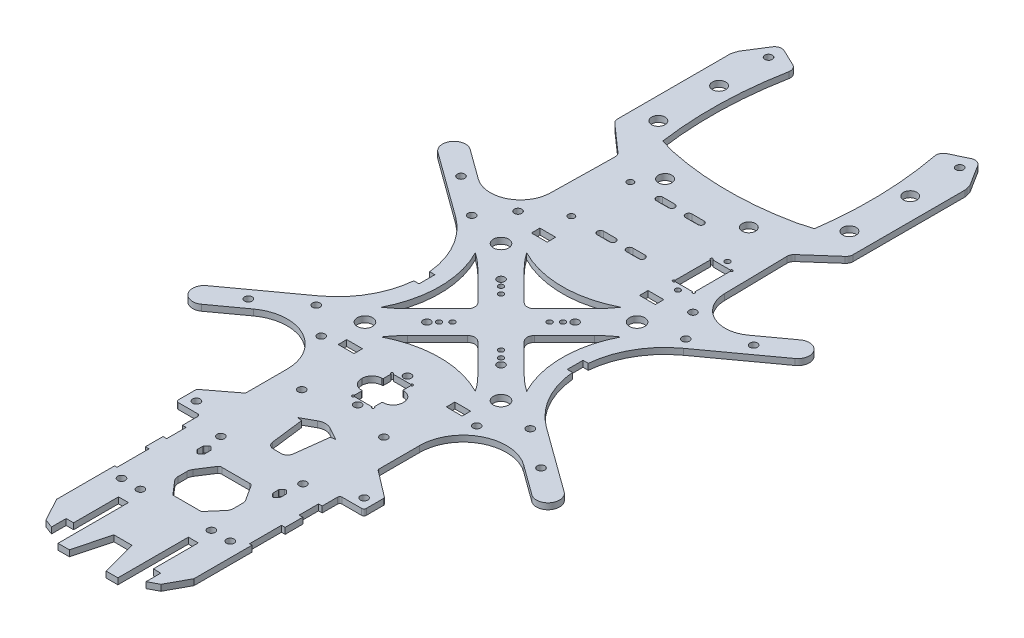
SolidWorks part; units mm, degrees
material "PPS"
ref_plane "前视基准面" through (0, 0, 0) normal (0, 0, 1) x (1, 0, 0)
ref_plane "上视基准面" through (0, 0, 0) normal (0, 1, 0) x (1, 0, 0)
ref_plane "右视基准面" through (0, 0, 0) normal (1, 0, 0) x (0, 0, -1)
sketch "草图1" plane through (0, 0, 0) normal (0, 1, 0) x (1, 0, 0)
  line L0 (-126.4995, 0) -> (116.8967, 0) construction
  line L1 (121.619, 121.619) -> (-121.619, -121.619) construction
  line L2 (0, 104.5414) -> (0, -99.6328) construction
  line L3 (-108.3893, 108.3893) -> (124.9236, -124.9236) construction
  line L4 (0, 0) -> (86.3378, -62.728) construction
  line L5 (21.4, 65.75) -> (28.6, 65.75)
  line L6 (20.9, 50.75) -> (20.9, 65.25)
  line L19 (21.4, 50.25) -> (28.6, 50.25)
  line L20 (35.3841, 83.6272) -> (48.4165, 95.1336)
  line L21 (0, 82.79) -> (0, 88.225) construction
  line L22 (17.0991, -107.7737) -> (17.0991, -105.6162)
  line L23 (-25.2781, 96.1111) -> (-31.2329, 97.7907)
  line L25 (27.2573, -95.1) -> (28.7573, -95.1) construction
  line L28 (15.9026, -104.2126) -> (16.9526, -105.2626)
  line L29 (14.1455, -105.2626) -> (15.1955, -104.2126)
  line L30 (-16.9545, -108.1273) -> (-15.9045, -109.1773)
  line L35 (73.5338, -47.5541) -> (46.853, -28.1694)
  line L36 (-15.1974, -109.1773) -> (-14.1474, -108.1273)
  line L37 (-14.0009, -105.6162) -> (-14.0009, -107.7737)
  line L38 (-14.1474, -105.2626) -> (-15.1974, -104.2126)
  line L39 (-48.4165, 95.1336) -> (-48.4165, 143.0516)
  line L40 (-35.3841, 83.6272) -> (-48.4165, 95.1336)
  line L42 (28.7573, -95.1) -> (28.7573, -102.35)
  line L59 (0, 72.0242) -> (0, 60.8242) construction
  line L64 (20.9, 58) -> (32.4846, 58) construction
  line L65 (25, 65.75) -> (25, 50.25) construction
  line L66 (29.1, 65.25) -> (29.1, 50.75)
  line L69 (-28.3, 64.3716) -> (-2.5276, 64.3716) construction
  line L72 (28.7573, -102.35) -> (27.2573, -102.35)
  line L80 (-15.9045, -104.2126) -> (-16.9545, -105.2626)
  line L81 (-17.1009, -107.7737) -> (-17.1009, -105.6162)
  line L82 (4.1009, -56.25) -> (4.1009, -53.2975)
  line L83 (-3.6009, -56.75) -> (3.6009, -56.75)
  line L84 (3.6009, -40.75) -> (-3.5991, -40.75)
  line L85 (4.1009, -41.25) -> (4.1009, -44.2025)
  line L86 (-4.1009, -56.25) -> (-4.1009, -53.2961)
  line L87 (-4.1009, -44.2011) -> (-4.1009, -41.2481)
  line L88 (-4.5484, -52.9461) -> (-4.4509, -52.9461)
  line L89 (-8.5484, -48.9461) -> (-8.5484, -48.5511)
  line L90 (8.5484, -48.9475) -> (8.5484, -48.5525)
  line L91 (4.4509, -52.9475) -> (4.5484, -52.9475)
  line L92 (4.5484, -44.5525) -> (4.4509, -44.5525)
  line L93 (-4.5484, -44.5511) -> (-4.4509, -44.5511)
  line L94 (13.9991, -105.6162) -> (13.9991, -107.7737)
  line L95 (15.1955, -109.1773) -> (14.1455, -108.1273)
  line L96 (16.9526, -108.1273) -> (15.9026, -109.1773)
  line L97 (18.9991, -62.5) -> (18.9991, -100.5) construction
  line L98 (18.9991, -100.5) -> (-19.0009, -100.5) construction
  line L99 (-19.0009, -62.5) -> (-19.0009, -100.5) construction
  line L100 (27.2573, -102.35) -> (27.2573, -110.35)
  line L101 (16.4174, -141.0041) -> (16.4174, -159.5041)
  line L102 (16.4174, -141.0041) -> (12.3174, -141.0041)
  line L103 (12.3174, -141.0041) -> (12.3174, -170.0041)
  line L104 (19.4666, -159.5041) -> (16.4174, -159.5041)
  line L105 (19.4666, -165.5542) -> (19.4666, -159.5041)
  line L106 (-3.8169, -155.5041) -> (-7.6919, -170.0041)
  line L107 (-7.6919, -170.0041) -> (-12.3174, -170.0041)
  line L108 (23.4926, -163.4505) -> (19.4666, -165.5542)
  line L109 (-19.4666, -165.5542) -> (-19.4666, -159.5041)
  line L110 (-19.4666, -159.5041) -> (-16.4174, -159.5041)
  line L111 (-12.3174, -141.0041) -> (-12.3174, -170.0041)
  line L112 (-16.4174, -141.0041) -> (-12.3174, -141.0041)
  line L113 (-16.4174, -141.0041) -> (-16.4174, -159.5041)
  line L114 (7.4592, -170.0041) -> (12.3174, -170.0041)
  line L115 (-3.8169, -155.5041) -> (3.6009, -155.5041)
  line L116 (3.6009, -155.5041) -> (7.4592, -170.0041)
  line L117 (-23.1028, -164.168) -> (-19.4666, -165.5542)
  line L118 (-10.8641, -115.9341) -> (-6.9283, -109.8213)
  line L119 (-10.5808, -123.7337) -> (-5.8541, -129.2069)
  line L120 (-5.8541, -129.2069) -> (5.8541, -129.2069)
  line L121 (-11.4015, -121.5278) -> (-11.4015, -117.7612)
  line L122 (27.2573, -110.35) -> (28.7573, -110.35)
  line L123 (28.2798, -130.7335) -> (28.2798, -154.6401)
  line L124 (28.2798, -154.6401) -> (23.4926, -163.4505)
  line L125 (-28.2798, -154.6401) -> (-23.1028, -164.168)
  line L126 (-28.2798, -130.7335) -> (-28.2798, -154.6401)
  line L127 (28.7573, -110.35) -> (28.7573, -117.6)
  line L128 (28.7573, -117.6) -> (27.2573, -117.6)
  line L129 (27.2573, -117.6) -> (27.2573, -130.7962)
  line L130 (27.2573, -130.7962) -> (28.2798, -130.7335)
  line L132 (-27.2573, -130.7962) -> (-28.2798, -130.7335)
  line L133 (-27.2573, -117.6) -> (-27.2573, -130.7962)
  line L134 (-28.7573, -117.6) -> (-27.2573, -117.6)
  line L135 (-28.7573, -110.35) -> (-28.7573, -117.6)
  line L136 (-27.2573, -110.35) -> (-28.7573, -110.35)
  line L137 (-27.2573, -102.35) -> (-27.2573, -110.35)
  line L138 (-28.7573, -102.35) -> (-27.2573, -102.35)
  line L139 (-28.7573, -95.1) -> (-28.7573, -102.35)
  line L140 (-27.2573, -95.1) -> (-28.7573, -95.1) construction
  line L142 (-73.5338, 47.5541) -> (-46.853, 28.1694)
  line L143 (-73.5338, -47.5541) -> (-46.853, -28.1694)
  line L149 (48.4165, 95.1336) -> (48.4165, 143.0516)
  line L150 (0, -114.8485) -> (0, -146.3095) construction
  line L151 (-5.6802, -109.2069) -> (5.6802, -109.2069)
  line L152 (10.5808, -123.7337) -> (5.8541, -129.2069)
  line L153 (11.4015, -121.5278) -> (11.4015, -117.7612)
  line L154 (10.8641, -115.9341) -> (6.9283, -109.8213)
  line L155 (-19.0009, -62.5) -> (18.9991, -62.5) construction
  line L166 (-11.2799, 76.5216) -> (-6.2799, 76.5216) construction
  line L169 (-11.2799, 77.8216) -> (-6.2799, 77.8216)
  line L170 (-11.2799, 75.2216) -> (-6.2799, 75.2216)
  line L171 (-11.2799, 52.2216) -> (-6.2799, 52.2216) construction
  line L172 (-11.2799, 50.9216) -> (-6.2799, 50.9216)
  line L173 (-11.2799, 53.5216) -> (-6.2799, 53.5216)
  line L174 (5.7201, 76.5216) -> (0.7201, 76.5216) construction
  line L175 (5.7201, 75.2216) -> (0.7201, 75.2216)
  line L176 (5.7201, 77.8216) -> (0.7201, 77.8216)
  line L177 (5.7201, 52.2216) -> (0.7201, 52.2216) construction
  line L178 (5.7201, 53.5216) -> (0.7201, 53.5216)
  line L179 (5.7201, 50.9216) -> (0.7201, 50.9216)
  line L180 (73.5338, 47.5541) -> (46.853, 28.1694)
  line L181 (44.0442, 32) -> (60.2246, 43.7557) construction
  line L183 (25.2781, 96.1111) -> (31.2329, 97.7907)
  line L184 (47.6512, 145.4189) -> (48.4165, 143.0516)
  line L188 (-47.6512, 145.4189) -> (-40.8875, 156.1591)
  line L190 (47.6512, 145.4189) -> (40.8875, 156.1591)
  line L192 (31.6811, 151.7709) -> (40.8875, 156.1591)
  line L193 (-40.8875, 156.1591) -> (-31.6811, 151.7709)
  line L194 (-47.6512, 145.4189) -> (-48.4165, 143.0516)
  line L195 (67.9498, 55.2397) -> (55.6247, 46.285)
  line L196 (35.3841, 83.6272) -> (35.8675, 56.1341)
  line L197 (-35.3841, 83.6272) -> (-35.8675, 56.1341)
  line L198 (-67.9498, 55.2397) -> (-55.6247, 46.285)
  line L199 (55.6018, -46.2684) -> (67.9498, -55.2397)
  line L200 (27.2573, -60.7106) -> (27.2573, -95.1) construction
  line L201 (-27.2573, -60.7106) -> (-27.2573, -95.1) construction
  line L202 (-55.6018, -46.2684) -> (-67.9498, -55.2397)
  line L203 (28.7573, -95.1) -> (38.6804, -95.1)
  line L204 (38.6804, -95.1) -> (38.6804, -86.6)
  line L205 (38.6804, -86.6) -> (27.2573, -77.9053)
  line L206 (27.2573, -60.7106) -> (27.2573, -77.9053)
  line L207 (-38.6804, -86.6) -> (-27.2573, -77.9053)
  line L208 (-38.6804, -95.1) -> (-38.6804, -86.6)
  line L209 (-28.7573, -95.1) -> (-38.6804, -95.1)
  line L210 (-27.2573, -60.7106) -> (-27.2573, -77.9053)
  circle A0 centre (10, 10) radius 1.075
  circle A1 centre (12.75, 12.75) radius 1.075
  circle A2 centre (15.25, 15.25) radius 1.55
  circle A3 centre (-15.25, 15.25) radius 1.55
  circle A4 centre (-12.75, 12.75) radius 1.075
  circle A5 centre (-10, 10) radius 1.075
  circle A6 centre (-10, -10) radius 1.075
  circle A7 centre (-12.75, -12.75) radius 1.075
  circle A8 centre (-15.25, -15.25) radius 1.55
  circle A9 centre (15.25, -15.25) radius 1.55
  circle A10 centre (12.75, -12.75) radius 1.075
  circle A11 centre (10, -10) radius 1.075
  circle A14 centre (28, -28) radius 3.15
  circle A15 centre (-28, -28) radius 3.15
  circle A16 centre (25, 68.2) radius 1.05
  arc A17 (20.9, 65.25) -> (21.4, 65.75) centre (20.9, 65.75) cw
  arc A18 (20.9, 50.75) -> (21.4, 50.25) centre (20.9, 50.25) ccw
  circle A31 centre (25, 47.8) radius 1.05
  circle A34 centre (17.238, 84.7633) radius 2.75
  circle A35 centre (-17.238, 84.7633) radius 2.75
  circle A36 centre (-39.335, 104.0823) radius 2.75
  circle A37 centre (-39.335, 129.0823) radius 2.75
  circle A38 centre (-28, 28) radius 3.15
  circle A39 centre (28, 28) radius 3.15
  circle A43 centre (44.0442, -32) radius 1.55
  circle A44 centre (60.2246, -43.7557) radius 1.55
  circle A47 centre (-60.2246, -43.7557) radius 1.55
  arc A63 (29.1, 65.25) -> (28.6, 65.75) centre (29.1, 65.75) ccw
  arc A64 (29.1, 50.75) -> (28.6, 50.25) centre (29.1, 50.25) cw
  circle A65 centre (-23.2799, 76.5216) radius 1.3
  circle A68 centre (-23.2799, 52.2216) radius 1.3
  circle A71 centre (-44.0442, -32) radius 1.55
  circle A72 centre (60.2246, 43.7557) radius 1.55
  circle A73 centre (44.0442, 32) radius 1.55
  circle A74 centre (-44.0442, 32) radius 1.55
  circle A75 centre (-60.2246, 43.7557) radius 1.55
  arc A76 (-11.2799, 77.8216) -> (-11.2799, 75.2216) centre (-11.2799, 76.5216) ccw
  arc A77 (67.9498, -55.2397) -> (73.5338, -47.5541) centre (70.7418, -51.3969) ccw
  arc A79 (-17.1009, -107.7737) -> (-16.9545, -108.1273) centre (-16.6009, -107.7737) ccw
  arc A80 (-15.9045, -109.1773) -> (-15.1974, -109.1773) centre (-15.5509, -108.8237) ccw
  arc A81 (-14.0009, -107.7737) -> (-14.1474, -108.1273) centre (-14.5009, -107.7737) cw
  arc A82 (-14.0009, -105.6162) -> (-14.1474, -105.2626) centre (-14.5009, -105.6162) ccw
  arc A83 (-15.1974, -104.2126) -> (-15.9045, -104.2126) centre (-15.5509, -104.5662) ccw
  arc A84 (-17.1009, -105.6162) -> (-16.9545, -105.2626) centre (-16.6009, -105.6162) cw
  arc A85 (-4.1009, -56.25) -> (-3.6009, -56.75) centre (-4.1009, -56.75) ccw
  arc A86 (4.1009, -56.25) -> (3.6009, -56.75) centre (4.1009, -56.75) cw
  arc A87 (4.1009, -41.25) -> (3.6009, -40.75) centre (4.1009, -40.75) ccw
  arc A88 (-4.1009, -41.2481) -> (-3.5991, -40.75) centre (-4.0991, -40.7481) cw
  arc A89 (8.5484, -48.5525) -> (4.5484, -44.5525) centre (4.5484, -48.5525) ccw
  arc A90 (-4.5484, -44.5511) -> (-8.5484, -48.5511) centre (-4.5484, -48.5511) ccw
  arc A91 (-4.5484, -52.9461) -> (-8.5484, -48.9461) centre (-4.5484, -48.9461) cw
  arc A92 (8.5484, -48.9475) -> (4.5484, -52.9475) centre (4.5484, -48.9475) cw
  arc A93 (4.1009, -44.2025) -> (4.4509, -44.5525) centre (4.4509, -44.2025) ccw
  arc A94 (4.1009, -53.2975) -> (4.4509, -52.9475) centre (4.4509, -53.2975) cw
  arc A95 (-4.1009, -44.2011) -> (-4.4509, -44.5511) centre (-4.4509, -44.2011) cw
  arc A96 (-4.1009, -53.2961) -> (-4.4509, -52.9461) centre (-4.4509, -53.2961) ccw
  arc A97 (17.0991, -107.7737) -> (16.9526, -108.1273) centre (16.5991, -107.7737) cw
  arc A98 (17.0991, -105.6162) -> (16.9526, -105.2626) centre (16.5991, -105.6162) ccw
  arc A99 (15.1955, -104.2126) -> (15.9026, -104.2126) centre (15.5491, -104.5662) cw
  arc A100 (13.9991, -105.6162) -> (14.1455, -105.2626) centre (14.4991, -105.6162) cw
  arc A101 (13.9991, -107.7737) -> (14.1455, -108.1273) centre (14.4991, -107.7737) ccw
  arc A102 (15.9026, -109.1773) -> (15.1955, -109.1773) centre (15.5491, -108.8237) cw
  circle A103 centre (-22.3899, -133.8062) radius 1.55
  circle A104 centre (22.3899, -133.8062) radius 1.55
  circle A105 centre (-16.9009, -98.4) radius 1.55
  circle A106 centre (16.8991, -98.4) radius 1.55
  arc A107 (-5.6802, -109.2069) -> (-6.9283, -109.8213) centre (-5.7932, -110.5521) ccw
  arc A108 (-11.4015, -117.7612) -> (-10.8641, -115.9341) centre (-8.0265, -117.7612) cw
  arc A109 (-10.5808, -123.7337) -> (-11.4015, -121.5278) centre (-8.0265, -121.5278) cw
  circle A110 centre (-14.6009, -133.8062) radius 1.55
  circle A111 centre (14.6009, -133.8062) radius 1.55
  arc A112 (10.5808, -123.7337) -> (11.4015, -121.5278) centre (8.0265, -121.5278) ccw
  arc A113 (11.4015, -117.7612) -> (10.8641, -115.9341) centre (8.0265, -117.7612) ccw
  arc A114 (5.6802, -109.2069) -> (6.9283, -109.8213) centre (5.7932, -110.5521) cw
  arc A132 (-6.2799, 75.2216) -> (-6.2799, 77.8216) centre (-6.2799, 76.5216) ccw
  arc A133 (-11.2799, 50.9216) -> (-11.2799, 53.5216) centre (-11.2799, 52.2216) cw
  arc A134 (-6.2799, 53.5216) -> (-6.2799, 50.9216) centre (-6.2799, 52.2216) cw
  arc A135 (5.7201, 75.2216) -> (5.7201, 77.8216) centre (5.7201, 76.5216) ccw
  arc A136 (0.7201, 77.8216) -> (0.7201, 75.2216) centre (0.7201, 76.5216) ccw
  arc A137 (5.7201, 53.5216) -> (5.7201, 50.9216) centre (5.7201, 52.2216) cw
  arc A138 (0.7201, 50.9216) -> (0.7201, 53.5216) centre (0.7201, 52.2216) cw
  circle A143 centre (-16.9009, -65.108) radius 1.55
  circle A144 centre (16.9009, -65.108) radius 1.55
  circle A145 centre (0, -38.5) radius 1.55
  circle A146 centre (0, -59) radius 1.55
  arc A147 (67.9498, 55.2397) -> (73.5338, 47.5541) centre (70.7418, 51.3969) cw
  arc A148 (46.853, 28.1694) -> (46.853, -28.1694) centre (67.3193, 0) ccw
  circle A149 centre (44.0442, -32) radius 6 construction
  arc A151 (-67.9498, 55.2397) -> (-73.5338, 47.5541) centre (-70.7418, 51.3969) ccw
  arc A153 (-46.853, 28.1694) -> (-46.853, -28.1694) centre (-67.3193, 0) cw
  arc A154 (-67.9498, -55.2397) -> (-73.5338, -47.5541) centre (-70.7418, -51.3969) cw
  circle A158 centre (39.335, 129.0823) radius 2.75
  circle A159 centre (39.335, 104.0823) radius 2.75
  arc A160 (-25.2781, 96.1111) -> (25.2781, 96.1111) centre (0, 215.2587) ccw
  circle A161 centre (-36, 43) radius 1.55
  circle A164 centre (36, 43) radius 1.55
  circle A165 centre (-32, -42) radius 1.55
  circle A166 centre (32, -42) radius 1.55
  circle A171 centre (-39.335, 149.4323) radius 1.55
  arc A176 (30.0249, 148.5011) -> (31.6811, 151.7709) centre (32.9719, 149.0628) cw
  arc A178 (30.0249, 148.5011) -> (31.2329, 97.7907) centre (-122.0773, 119.5082) cw
  arc A180 (-30.0249, 148.5011) -> (-31.2329, 97.7907) centre (122.0773, 119.5082) ccw
  arc A181 (-31.6811, 151.7709) -> (-30.0249, 148.5011) centre (-32.9719, 149.0628) cw
  arc A182 (55.6247, 46.285) -> (35.8675, 56.1341) centre (48.31, 56.3528) cw
  arc A183 (-55.6247, 46.285) -> (-35.8675, 56.1341) centre (-48.31, 56.3528) ccw
  circle A185 centre (39.335, 149.4323) radius 1.55
  arc A186 (55.6018, -46.2684) -> (27.2573, -60.7106) centre (45.1089, -60.7106) ccw
  arc A187 (-55.6018, -46.2684) -> (-27.2573, -60.7106) centre (-45.1089, -60.7106) cw
  circle A188 centre (34.5, -90.85) radius 1.55
  circle A189 centre (-34.5, -90.85) radius 1.55
  point P47 (-8.7799, 76.5216)
  point P104 (-32.5, 0)
  point P105 (32.5, 0)
  point P110 (3.2201, 76.5216)
  point P115 (-8.7799, 52.2216)
  point P171 (3.2201, 52.2216)
  point P214 (38.6804, -90.85)
  point P215 (0, 0)
  point P354 (0, -129.2069)
  point P361 (7.3036, -118.1341)
  point P364 (0, -109.2069)
  dimension "D2" = 2.15
  dimension "D5" = 3.1
  dimension "D7" = 3.1
  dimension "D8" = 36
  dimension "D10" = 0.5
  dimension "D11" = 3.1
  dimension "D20" = 2.6
  dimension "D22" = 3.1
  dimension "D32" = 7.25
  dimension "D12" = 12
  dimension "D15" = 12
  dimension "D13" = 5
  dimension "D9" = 3.1
  dimension "D25" = 4.75
  dimension "D26" = 13
  dimension "D31" = 12
  dimension "D41" = 96.833
  dimension "D49" = 32
  dimension "D54" = 45.35
  dimension "D59" = 8.5
  dimension "D61" = 6.3
  dimension "D3" = 10
  dimension "D4" = 2.75
  dimension "D6" = 2.5
  dimension "D14" = 58
  dimension "D16" = 2.608
  dimension "D17" = 15.5
  dimension "D18" = 2.45
  dimension "D19" = 8.2
  dimension "D21" = 24.3
  dimension "D23" = 2.25
  dimension "D24" = 2.25
  dimension "D27" = 20
  dimension "D28" = 25
  dimension "D29" = 25
  dimension "D30" = 32
  dimension "D33" = 1.5
  dimension "D34" = 2.1
  dimension "D35" = 10.5
  dimension "D36" = 14.5
  dimension "D37" = 4
  dimension "D38" = 4.1
  dimension "D39" = 8
  dimension "D40" = 65
  dimension "D42" = 70.7683
  dimension "D43" = 43
  dimension "D44" = 20
  dimension "D45" = 40.75
  dimension "D46" = 7.2
  dimension "D47" = 16
  dimension "D48" = 62.5
  dimension "D50" = 38
  dimension "D51" = 7.2
  dimension "D52" = 36
  dimension "D53" = 42
  dimension "D55" = 90.85
  dimension "D56" = 83.6272
  dimension "D57" = 11.5064
  dimension "D58" = 34.5
  dimension "D60" = 56
extrude "凸台-拉伸1" add sketch "草图1" along normal blind 2.5
sketch "草图6" plane through (0, 2.5, 0) normal (0, 1, 0) x (1, 0, 0)
  line L1 (-23.978, 14.4296) -> (-9.5485, 0)
  line L2 (-126.4995, 0) -> (116.8967, 0) construction
  line L3 (-58.8867, 0) -> (57.6096, 0) construction
  line L4 (-23.978, -14.4296) -> (-9.5485, 0)
  line L5 (0, 29.8455) -> (0, -115.5328) construction
  line L6 (0, 104.5414) -> (0, -99.6328) construction
  line L14 (14.4296, 23.978) -> (0, 9.5485)
  line L15 (-14.4296, 23.978) -> (0, 9.5485)
  line L20 (2.5276, -72.9435) -> (7.8986, -75.8938)
  line L21 (-7.8986, -75.8938) -> (-2.5276, -72.9435)
  line L22 (-1.6288, -92.0995) -> (1.6288, -92.0995)
  line L23 (-5.924, -76.1216) -> (-4.2339, -89.7964)
  line L24 (5.924, -76.1216) -> (4.2339, -89.7964)
  line L25 (-7.8986, -75.8938) -> (-5.924, -76.1216)
  line L26 (7.8986, -75.8938) -> (5.924, -76.1216)
  line L27 (23.978, -14.4296) -> (9.5485, 0)
  line L28 (23.978, 14.4296) -> (9.5485, 0)
  line L29 (-14.4296, -23.978) -> (0, -9.5485)
  line L30 (14.4296, -23.978) -> (0, -9.5485)
  arc A3 (-23.978, 14.4296) -> (-29.9602, 19.3706) centre (-52.8883, -14.4807) ccw
  arc A5 (-23.978, -14.4296) -> (-29.9602, -19.3706) centre (-52.8883, 14.4807) cw
  arc A6 (-29.9602, -19.3706) -> (-29.9602, 19.3706) centre (-67.3193, 0) ccw
  arc A18 (-14.4296, 23.978) -> (-19.3706, 29.9602) centre (14.4807, 52.8883) cw
  arc A19 (-19.3706, 29.9602) -> (19.3706, 29.9602) centre (0, 67.3193) ccw
  arc A20 (14.4296, 23.978) -> (19.3706, 29.9602) centre (-14.4807, 52.8883) ccw
  arc A27 (2.5276, -72.9435) -> (-2.5276, -72.9435) centre (0, -77.545) ccw
  arc A28 (1.6288, -92.0995) -> (4.2339, -89.7964) centre (1.6288, -89.4745) ccw
  arc A29 (-1.6288, -92.0995) -> (-4.2339, -89.7964) centre (-1.6288, -89.4745) cw
  arc A30 (23.978, 14.4296) -> (29.9602, 19.3706) centre (52.8883, -14.4807) cw
  arc A31 (29.9602, 19.3706) -> (29.9602, -19.3706) centre (67.3193, 0) ccw
  arc A32 (23.978, -14.4296) -> (29.9602, -19.3706) centre (52.8883, 14.4807) ccw
  arc A33 (14.4296, -23.978) -> (19.3706, -29.9602) centre (-14.4807, -52.8883) cw
  arc A34 (19.3706, -29.9602) -> (-19.3706, -29.9602) centre (0, -67.3193) ccw
  arc A35 (-14.4296, -23.978) -> (-19.3706, -29.9602) centre (14.4807, -52.8883) ccw
  dimension "D1" = 45
  dimension "D2" = 4
extrude "减重" cut sketch "草图6" against normal up to next
fillet "圆角1" radius 3 14 edges at (-25.2781, 1.25, -96.1111) (25.2781, 1.25, -96.1111) (48.4165, 1.25, -95.1336) (-48.4165, 1.25, -95.1336) (-9.5485, 1.25, 0) (9.5485, 1.25, 0) (0, 1.25, -9.5485) (0, 1.25, 9.5485) (48.4165, 1.25, -143.0516) (40.8875, 1.25, -156.1591) (-48.4165, 1.25, -143.0516) (-40.8875, 1.25, -156.1591) (-35.3841, 1.25, -83.6272) (35.3841, 1.25, -83.6272)
sketch "草图7" plane through (0, 2.5, 0) normal (0, 1, 0) x (1, 0, 0)
  line L0 (-81.2345, 0) -> (102.1666, 0) construction
  line L1 (0, 63.5408) -> (0, -83.9036) construction
  line L2 (34, -3.25) -> (30.5, -3.25)
  line L3 (-34, 3.25) -> (-30.5, 3.25)
  line L4 (-34, 3.25) -> (-34, -3.25)
  line L5 (-34, -3.25) -> (-30.5, -3.25)
  line L6 (-30.5, 3.25) -> (-30.5, -3.25)
  line L7 (30.5, 3.25) -> (30.5, -3.25)
  line L8 (34, 3.25) -> (30.5, 3.25)
  line L9 (34, 3.25) -> (34, -3.25)
  line L10 (19, -38) -> (25.5, -38)
  line L11 (-25.5, 41.5) -> (-19, 41.5)
  line L12 (-25.5, 41.5) -> (-25.5, 38)
  line L13 (-25.5, 38) -> (-19, 38)
  line L14 (-19, 41.5) -> (-19, 38)
  line L15 (19, -38) -> (19, -41.5)
  line L16 (19, -41.5) -> (25.5, -41.5)
  line L17 (25.5, -38) -> (25.5, -41.5)
  line L18 (-19, -38) -> (-19, -41.5)
  line L19 (-19, -41.5) -> (-25.5, -41.5)
  line L20 (-25.5, -38) -> (-25.5, -41.5)
  line L21 (-19, -38) -> (-25.5, -38)
  line L22 (25.5, 38) -> (19, 38)
  line L23 (19, 41.5) -> (19, 38)
  line L24 (25.5, 41.5) -> (19, 41.5)
  line L25 (25.5, 41.5) -> (25.5, 38)
  point P26 (19, -39.75)
  dimension "D1" = 3.5
  dimension "D2" = 6.5
  dimension "D3" = 30.5
  dimension "D4" = 38
  dimension "D5" = 19
  dimension "D6" = 38
extrude "保护壳固定点" cut sketch "草图7" against normal up to next
fillet "圆角2" radius 1 8 edges at (-28.7573, 1.25, 95.1) (-38.6804, 1.25, 95.1) (-38.6804, 1.25, 86.6) (-27.2573, 1.25, 77.9053) (27.2573, 1.25, 77.9053) (38.6804, 1.25, 86.6) (38.6804, 1.25, 95.1) (28.7573, 1.25, 95.1)
